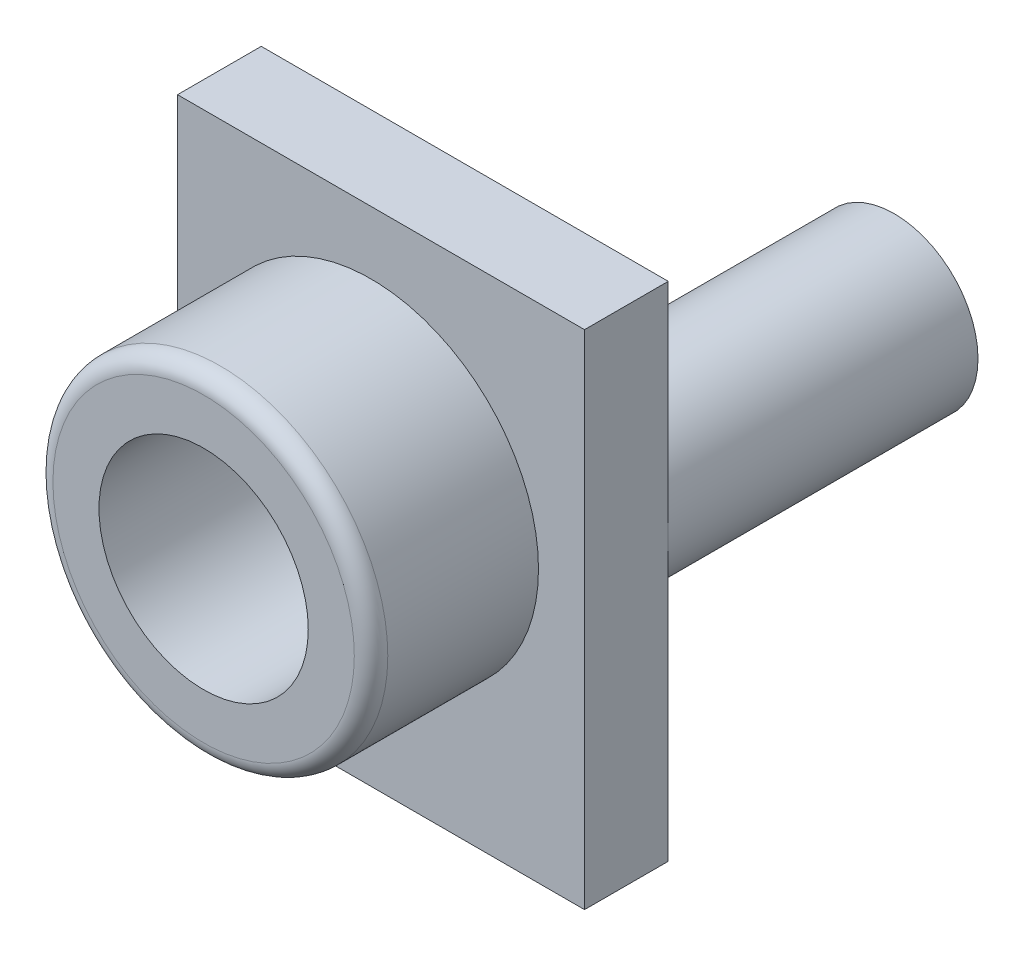
SolidWorks part; units mm, degrees
ref_plane "Спереди" through (0, 0, 0) normal (0, 0, 1) x (1, 0, 0)
ref_plane "Сверху" through (0, 0, 0) normal (0, 1, 0) x (1, 0, 0)
ref_plane "Справа" through (0, 0, 0) normal (1, 0, 0) x (0, 0, -1)
other "Configuration Table"
sketch "Эскиз1" plane through (0, 0, 0) normal (0, 0, 1) x (1, 0, 0)
  line L0 (4.8616, -6) -> (4.8616, 6)
  line L1 (4.8616, 6) -> (-4.8616, 6)
  line L2 (-4.8616, 6) -> (-4.8616, -6)
  line L3 (-4.8616, -6) -> (4.8616, -6)
  circle A0 centre (-0.2384, 0.5) radius 4
  circle A1 centre (-0.2384, 0.5) radius 2.5
  circle A2 centre (2.8616, 0.7) radius 2
sketch "Эскиз2" plane through (0, 0, 0) normal (0, 0, 1) x (1, 0, 0)
  line L0 (-4.8616, -6) -> (4.8616, -6) construction
  line L1 (4.8616, -6) -> (4.8616, 6) construction
  line L2 (4.8616, 6) -> (-4.8616, 6) construction
  line L3 (-4.8616, 6) -> (-4.8616, -6) construction
  line L4 (-4.8616, -6) -> (4.8616, -6)
  line L5 (4.8616, -6) -> (4.8616, 6)
  line L6 (4.8616, 6) -> (-4.8616, 6)
  line L7 (-4.8616, 6) -> (-4.8616, -6)
extrude "Бобышка-Вытянуть1" add sketch "Эскиз2" along normal blind 2
sketch "Эскиз3" plane through (0, 0, 2) normal (0, 0, 1) x (1, 0, 0)
  circle A0 centre (-0.2384, 0.5) radius 2.5 construction
  circle A1 centre (-0.2384, 0.5) radius 4 construction
  circle A2 centre (-0.2384, 0.5) radius 2.5
  circle A3 centre (-0.2384, 0.5) radius 4
extrude "Бобышка-Вытянуть2" add sketch "Эскиз3" along normal blind 4
sketch "Эскиз4" plane through (0, 0, 0) normal (0, 0, -1) x (-1, 0, 0)
  circle A0 centre (-2.8616, 0.7) radius 2 construction
  circle A1 centre (-2.8616, 0.7) radius 2
extrude "Бобышка-Вытянуть3" add sketch "Эскиз4" along normal blind 7.4
fillet "Скругление1" radius 0.4 1 edges at (3.7616, 0.5, 6)
sketch "hole" plane through (0, 0, 6) normal (0, 0, 1) x (1, 0, 0)
  circle A0 centre (-0.2384, 0.5) radius 2.5 construction
  circle A1 centre (-0.2384, 0.5) radius 2.5
sketch "Эскиз5" plane through (0, 0, 2) normal (0, 0, 1) x (1, 0, 0)
  circle A0 centre (-0.2384, 0.5) radius 1.1
  dimension "D1" = 2.2
extrude "Вырез-Вытянуть1" cut sketch "Эскиз5" against normal blind 2
